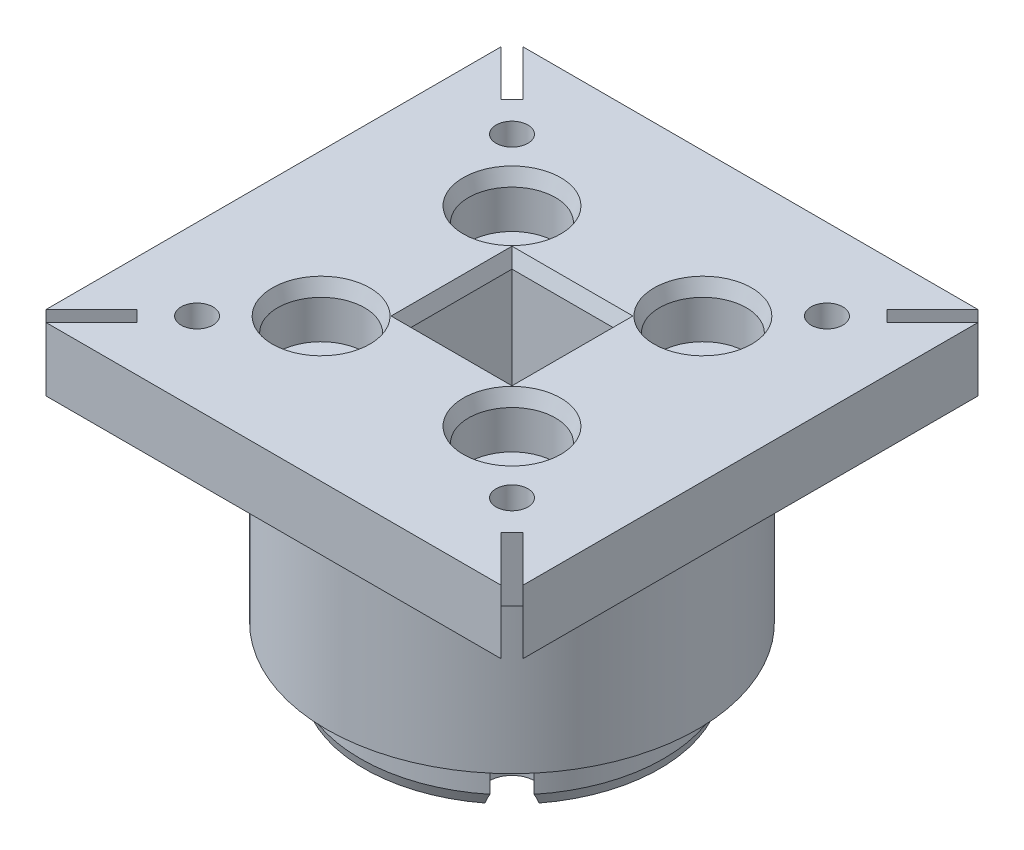
SolidWorks part; units mm, degrees
ref_plane "Спереди" through (0, 0, 0) normal (0, 0, 1) x (1, 0, 0)
ref_plane "Сверху" through (0, 0, 0) normal (0, 1, 0) x (1, 0, 0)
ref_plane "Справа" through (0, 0, 0) normal (1, 0, 0) x (0, 0, -1)
sketch "Sketch1" plane through (0, 0, 0) normal (0, 1, 0) x (1, 0, 0)
  circle A0 centre (0, 0) radius 17.5
  dimension "D1" = 35
extrude "Boss-Extrude1" add sketch "Sketch1" along normal blind 25
sketch "Sketch3" plane through (0, 0, 0) normal (0, -1, 0) x (1, 0, 0)
  circle A0 centre (0, 0) radius 14.3
  circle A1 centre (0, 0) radius 17.5 construction
  dimension "D1" = 3.2
extrude "Boss-Extrude2" add sketch "Sketch3" along normal blind 5
sketch "Sketch4" plane through (0, 25, 0) normal (0, 1, 0) x (1, 0, 0)
  line L1 (-5.2, 5.2) -> (5.2, 5.2)
  line L2 (-5.2, 5.2) -> (-5.2, -5.2)
  line L3 (-5.2, -5.2) -> (5.2, -5.2)
  line L4 (5.2, 5.2) -> (5.2, -5.2)
  line L5 (-5.2, 5.2) -> (5.2, -5.2) construction
  line L6 (-5.2, -5.2) -> (5.2, 5.2) construction
  point P0 (0, 0)
  dimension "D1" = 10.4
extrude "Cut-Extrude1" cut sketch "Sketch4" against normal through all
sketch "Sketch6" plane through (0, 25, 0) normal (0, 1, 0) x (1, 0, 0)
  line L1 (-9, 9) -> (9, 9) construction
  line L2 (-9, 9) -> (-9, -9) construction
  line L3 (-9, -9) -> (9, -9) construction
  line L4 (9, 9) -> (9, -9) construction
  line L5 (-9, 9) -> (9, -9) construction
  line L6 (-9, -9) -> (9, 9) construction
  circle A0 centre (9, -9) radius 2.1
  circle A1 centre (-9, -9) radius 2.1
  circle A2 centre (-9, 9) radius 2.1
  circle A3 centre (9, 9) radius 2.1
  point P0 (0, 0)
  dimension "D1" = 4.2
  dimension "D2" = 18
extrude "Cut-Extrude2" cut sketch "Sketch6" against normal through all
chamfer "Chamfer1" distance 1 angle 20 4 edges at (14.3, -5, 0) (0, -5, -14.3) (-14.3, -5, 0) (0, -5, 14.3) first distance on face at (12.7, -2.5, 0) first distance on face at (0, -2.5, -12.7) first distance on face at (-12.7, -2.5, 0) first distance on face at (0, -2.5, 12.7)
sketch "Sketch7" plane through (0, 25, 0) normal (0, 1, 0) x (1, 0, 0)
  circle A0 centre (9, 9) radius 4.1
  circle A1 centre (-9, 9) radius 4.1
  circle A2 centre (-9, -9) radius 4.1
  circle A3 centre (9, -9) radius 4.1
  dimension "D1" = 8.2
extrude "Cut-Extrude3" cut sketch "Sketch7" against normal blind 5
chamfer "Chamfer2" distance 0.5 angle 70 4 edges at (0, 25, -5.2) (5.2, 25, 0) (0, 25, 5.2) (-5.2, 25, 0) first distance on face at (-9, 25, -4.9)
sketch "Sketch8" plane through (0, 25, 0) normal (0, 1, 0) x (1, 0, 0)
  line L1 (22.5, 22.5) -> (-22.5, 22.5)
  line L2 (22.5, 22.5) -> (22.5, -22.5)
  line L3 (22.5, -22.5) -> (-22.5, -22.5)
  line L4 (-22.5, 22.5) -> (-22.5, -22.5)
  line L5 (22.5, 22.5) -> (-22.5, -22.5) construction
  line L6 (22.5, -22.5) -> (-22.5, 22.5) construction
  circle A0 centre (0, 0) radius 17.5
  circle A1 centre (0, 0) radius 17.5 construction
  circle A2 centre (-14.8492, -14.8492) radius 1.5
  circle A3 centre (-14.8492, 14.8492) radius 1.5
  circle A4 centre (14.8492, 14.8492) radius 1.5
  circle A5 centre (14.8492, -14.8492) radius 1.5
  circle A6 centre (0, 0) radius 21 construction
  point P18 (0, 0)
  point P19 (0, 0)
  point P20 (0, 0)
  point P21 (0, 0)
  circle M12 centre (0, 0) radius 17.5
  dimension "D1" = 3
  dimension "D2" = 42
  dimension "D3" = 45
extrude "Boss-Extrude3" add sketch "Sketch8" against normal blind 6 contours L4 L3 A2 M12 | L3 L2 A5 M12 | L2 L1 A4 M12 | L1 L4 A3 M12 region at (21.8636, 25, 0)
sketch "Sketch10" plane through (0, 25, 0) normal (0, 1, 0) x (1, 0, 0)
  line L0 (-22.5, -22.5) -> (22.5, 22.5) construction
  line L1 (-22.5, 22.5) -> (22.5, -22.5) construction
  line L2 (-18.208, -17.1473) -> (-17.1473, -18.208)
  line L3 (-17.1473, -18.208) -> (-21.4393, -22.5)
  line L4 (22.5, -22.5) -> (-22.5, -22.5) construction
  line L5 (-21.4393, -22.5) -> (-22.5, -22.5)
  line L6 (-22.5, -22.5) -> (-22.5, -21.4393)
  line L7 (-22.5, -21.4393) -> (-18.208, -17.1473)
  line L8 (-22.5, 21.4393) -> (-18.208, 17.1473)
  line L9 (-22.5, 22.5) -> (-22.5, -22.5) construction
  line L10 (-18.208, 17.1473) -> (-17.1473, 18.208)
  line L11 (-17.1473, 18.208) -> (-21.4393, 22.5)
  line L12 (22.5, 22.5) -> (-22.5, 22.5) construction
  line L13 (-21.4393, 22.5) -> (-22.5, 22.5)
  line L14 (-22.5, 22.5) -> (-22.5, 21.4393)
  line L15 (21.4393, 22.5) -> (17.1473, 18.208)
  line L16 (17.1473, 18.208) -> (18.208, 17.1473)
  line L17 (18.208, 17.1473) -> (22.5, 21.4393)
  line L18 (22.5, 22.5) -> (22.5, -22.5) construction
  line L19 (22.5, 21.4393) -> (22.5, 22.5)
  line L20 (22.5, 22.5) -> (21.4393, 22.5)
  line L21 (17.1473, -18.208) -> (18.208, -17.1473)
  line L22 (18.208, -17.1473) -> (22.5, -21.4393)
  line L23 (22.5, -21.4393) -> (22.5, -22.5)
  line L24 (22.5, -22.5) -> (21.4393, -22.5)
  line L25 (21.4393, -22.5) -> (17.1473, -18.208)
  circle A0 centre (-14.8492, -14.8492) radius 1.5 construction
  point P10 (-17.6777, -17.6777)
  point P19 (-17.6777, 17.6777)
  point P26 (17.6777, 17.6777)
  point P33 (17.6777, -17.6777)
  dimension "D1" = 4
  dimension "D2" = 1.5
extrude "Cut-Extrude4" cut sketch "Sketch10" against normal through all
chamfer "Chamfer3" distance 0.5 angle 70 4 edges at (9, 25, -4.9) (-9, 25, -4.9) (-9, 25, 13.1) (9, 25, 13.1) first distance on face at (0, 25, 0)
